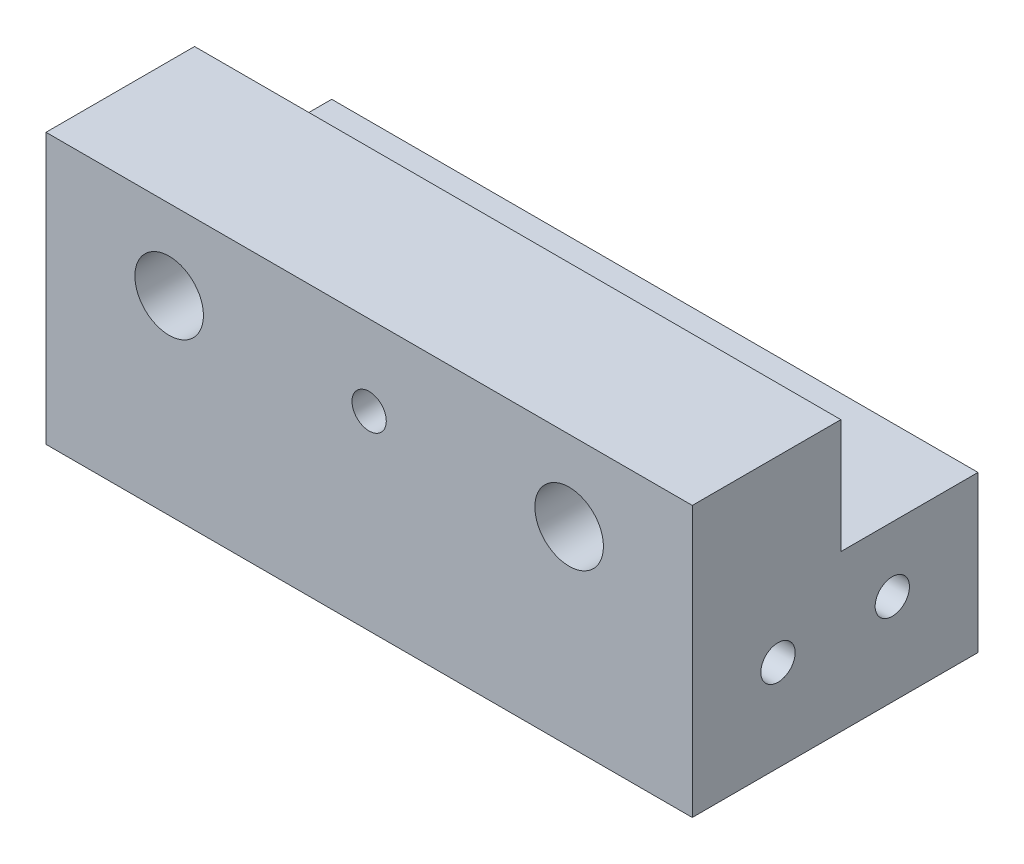
SolidWorks part; units mm, degrees
material "6061-T6 (SS)"
ref_plane "X-Y Datum" through (0, 0, 0) normal (0, 0, 1) x (1, 0, 0)
ref_plane "X-Z Datum" through (0, 0, 0) normal (0, 1, 0) x (1, 0, 0)
ref_plane "Y-Z Datum" through (0, 0, 0) normal (1, 0, 0) x (0, 0, -1)
sketch "Sketch1" plane through (0, 0, 0) normal (0, 0, 1) x (1, 0, 0)
  line L1 (-28.275, 11.825) -> (28.275, 11.825)
  line L2 (-28.275, 11.825) -> (-28.275, -11.825)
  line L3 (-28.275, -11.825) -> (28.275, -11.825)
  line L4 (28.275, 11.825) -> (28.275, -11.825)
  line L5 (-28.275, 11.825) -> (28.275, -11.825) construction
  line L6 (-28.275, -11.825) -> (28.275, 11.825) construction
  point P0 (0, 0)
  dimension "D1" = 56.55
  dimension "D2" = 23.65
extrude "Boss-Extrude1" add sketch "Sketch1" along normal blind 25 contours L2 L3 L4 L1
sketch "Sketch2" plane through (0, 0, 25) normal (0, 0, 1) x (1, 0, 0)
  line L0 (-23.5453, 4.825) -> (31.0951, 4.825) construction
  line L1 (0, 11.825) -> (0, -11.825) construction
  line L2 (-28.275, 11.825) -> (28.275, 11.825) construction
  line L3 (-17.5, 4.825) -> (17.5, 4.825) construction
  line L4 (-28.275, -11.825) -> (28.275, -11.825) construction
  circle A0 centre (17.5, 4.825) radius 3
  circle A1 centre (-17.5, 4.825) radius 3
  circle A2 centre (0, 4.825) radius 1.5
  point P10 (0, 4.825)
  dimension "D1" = 6
  dimension "D4" = 3
  dimension "D2" = 35
  dimension "D3" = 7
extrude "Cut-Extrude1" cut sketch "Sketch2" against normal blind 10 contours A1 L0 L3 | L0 A1 L3 | L0 L3 A0 | L3 L0 A0 | A2 region at (17.5, 4.825, 25) region at (-17.5, 4.825, 25) region at (0, 4.825, 25)
sketch "Sketch3" plane through (-28.275, 0, 0) normal (-1, 0, 0) x (0, 0, 1)
  line L0 (0, -3.825) -> (25, -3.825) construction
  line L1 (0, 11.825) -> (0, -11.825) construction
  line L2 (25, 182.425) -> (25, -15) construction
  line L3 (17.5, -3.825) -> (7.5, -3.825) construction
  line L4 (12.5, 11.825) -> (12.5, -11.825) construction
  line L5 (25, 11.825) -> (0, 11.825) construction
  line L6 (25, -11.825) -> (0, -11.825) construction
  line L7 (-274.7, -11.825) -> (25, -11.825) construction
  circle A0 centre (17.5, -3.825) radius 1.5
  circle A1 centre (7.5, -3.825) radius 1.5
  point P10 (12.5, -3.825)
  dimension "D1" = 3
  dimension "D2" = 10
  dimension "D3" = 8
extrude "Cut-Extrude2" cut sketch "Sketch3" against normal through all
sketch "Sketch4" plane through (-28.275, 0, 0) normal (-1, 0, 0) x (0, 0, 1)
  line L1 (0, 11.825) -> (12, 11.825)
  line L2 (0, 11.825) -> (0, 1.825)
  line L3 (0, 1.825) -> (12, 1.825)
  line L4 (12, 11.825) -> (12, 1.825)
  dimension "D1" = 12
  dimension "D2" = 10
extrude "Cut-Extrude3" cut sketch "Sketch4" against normal through all
